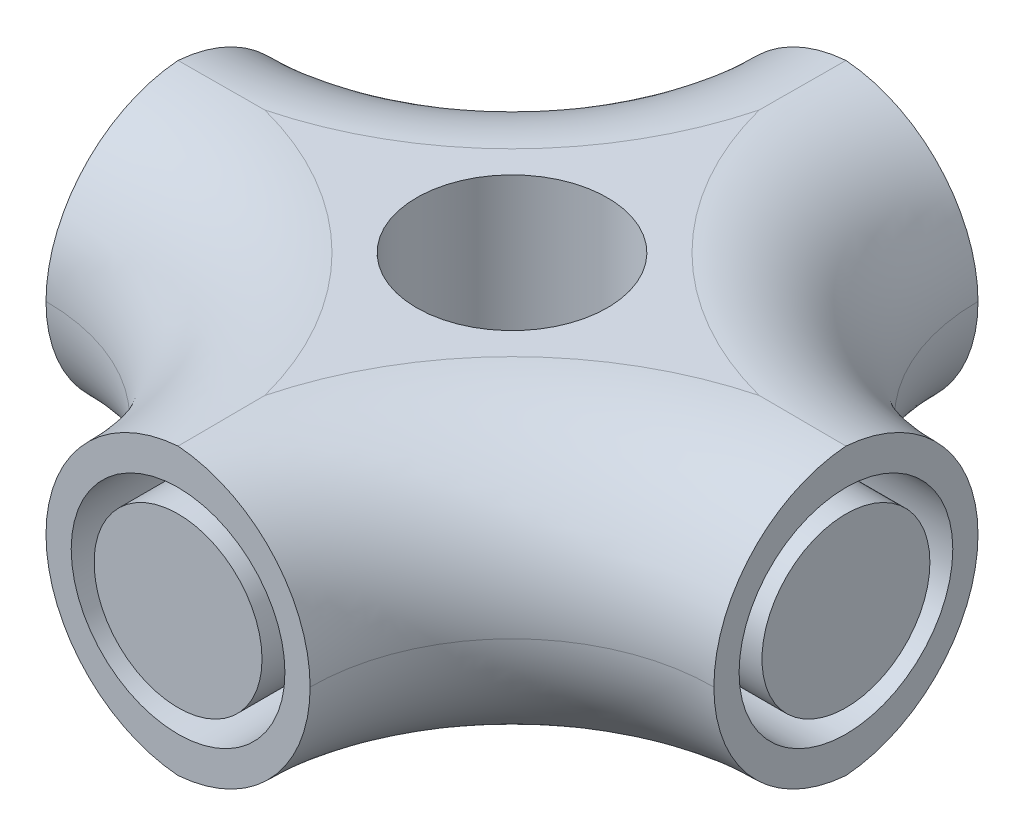
SolidWorks part; units mm, degrees
ref_plane "Ön Düzlem" through (0, 0, 0) normal (0, 0, 1) x (1, 0, 0)
ref_plane "Üst Düzlem" through (0, 0, 0) normal (0, 1, 0) x (1, 0, 0)
ref_plane "Sağ Düzlem" through (0, 0, 0) normal (1, 0, 0) x (0, 0, -1)
sketch "Sketch3" plane through (0, 0, 0) normal (0, 1, 0) x (1, 0, 0)
  line L1 (-17.5, 17.5) -> (17.5, 17.5)
  line L2 (-17.5, 17.5) -> (-17.5, -17.5)
  line L3 (-17.5, -17.5) -> (17.5, -17.5)
  line L4 (17.5, 17.5) -> (17.5, -17.5)
  line L5 (-17.5, 17.5) -> (17.5, -17.5) construction
  line L6 (-17.5, -17.5) -> (17.5, 17.5) construction
  circle A0 centre (0, 0) radius 5
  dimension "D2" = 10
  dimension "D1" = 35
extrude "Yükseklik-Ekstrüzyon1" add sketch "Sketch3" along normal blind 15
sketch "Çizim1" plane through (0, 0, 17.5) normal (0, 0, 1) x (1, 0, 0)
  line L0 (17.5, 15) -> (17.5, 0) construction
  circle A0 centre (0, 7.5) radius 5.6
  circle A2 centre (0, 7.5) radius 4.4
  point P5 (17.5, 7.5)
  dimension "D1" = 11.2
  dimension "D2" = 1.2
extrude "Kes-Ekstrüzyon2" cut sketch "Çizim1" against normal blind 10
pattern_circular "Dairesel Kaplama1" count 4 over 360 about axis through (0, 15, 0) along (0, -1, 0) of "Kes-Ekstrüzyon2" reverse direction yes
sketch "Çizim3" plane through (0, 15, 0) normal (0, 1, 0) x (1, 0, 0)
  line L0 (-17.5, -17.5) -> (17.5, -17.5) construction
  line L1 (-17.5, 17.5) -> (-17.5, -17.5) construction
  line L2 (-17.5, -6.9204) -> (-17.5, -17.5)
  line L3 (-17.5, -17.5) -> (-6.9204, -17.5)
  arc A0 (-17.5, -6.9204) -> (-6.9204, -17.5) centre (-17.5, -17.5) cw
  line M3 (-17.5, 17.5) -> (-17.5, -17.5)
  line M4 (-17.5, -17.5) -> (17.5, -17.5)
extrude "Kes-Ekstrüzyon3" cut sketch "Çizim3" against normal through all contours A0 M3 M4 region at (-13.0099, 15, 13.0099)
pattern_circular "Dairesel Kaplama3" count 4 over 360 about axis through (0, 15, 0) along (0, -1, 0) of "Kes-Ekstrüzyon3"
fillet "Radyus3" radius 7.5 8 edges at (-10.0191, 15, 10.0191) (-10.0191, 0, 10.0191) (-10.0191, 15, -10.0191) (10.0191, 15, -10.0191) (10.0191, 15, 10.0191) (10.0191, 0, 10.0191) (10.0191, 0, -10.0191) (-10.0191, 0, -10.0191)
sketch "Çizim4" plane through (0, 0, 0) normal (0, 1, 0) x (1, 0, 0)
  circle A0 centre (0, 0) radius 2.5
  circle A1 centre (0, 0) radius 5 construction
  circle A2 centre (0, 0) radius 5
  dimension "D1" = 5
extrude "Yükseklik-Ekstrüzyon2" add sketch "Çizim4" along normal blind 3
